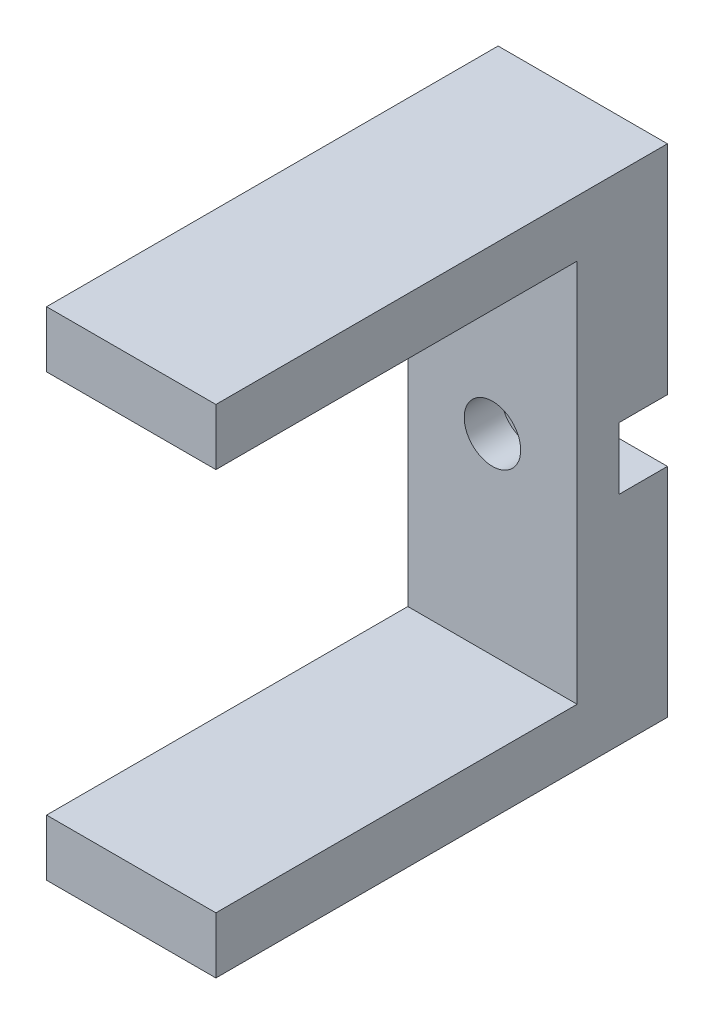
SolidWorks part; units mm, degrees
ref_plane "Front Plane" through (0, 0, 0) normal (0, 0, 1) x (1, 0, 0)
ref_plane "Top Plane" through (0, 0, 0) normal (0, 1, 0) x (1, 0, 0)
ref_plane "Right Plane" through (0, 0, 0) normal (1, 0, 0) x (0, 0, -1)
sketch "Sketch1" plane through (0, 0, 0) normal (0, 0, 1) x (1, 0, 0)
  line L1 (-12.2414, -9.222) -> (-27.2414, -9.222)
  line L2 (-12.2414, -9.222) -> (-12.2414, 34.778)
  line L3 (-12.2414, 34.778) -> (-27.2414, 34.778)
  line L4 (-27.2414, -9.222) -> (-27.2414, 34.778)
  dimension "D1" = 44
  dimension "D2" = 15
extrude "Extrude1" add sketch "Sketch1" along normal blind 40
sketch "Sketch2" plane through (0, 0, 40) normal (0, 0, 1) x (1, 0, 0)
  line L0 (-12.2414, -9.222) -> (-12.2414, 34.778) construction
  line L1 (-12.2414, 29.778) -> (-27.2414, 29.778)
  line L2 (-12.2414, 29.778) -> (-12.2414, -4.222)
  line L3 (-12.2414, -4.222) -> (-27.2414, -4.222)
  line L4 (-27.2414, 29.778) -> (-27.2414, -4.222)
  line L5 (-27.2414, 34.778) -> (-27.2414, -9.222) construction
  line L6 (-12.2414, 34.778) -> (-27.2414, 34.778) construction
  line L7 (-27.2414, -9.222) -> (-12.2414, -9.222) construction
  dimension "D1" = 5
  dimension "D2" = 5
extrude "Cut-Extrude1" cut sketch "Sketch2" against normal blind 32
sketch "Sketch3" plane through (0, 0, 0) normal (0, 0, -1) x (-1, 0, 0)
  line L0 (27.2414, 34.778) -> (27.2414, -9.222) construction
  line L1 (22.4914, 10.028) -> (27.2414, 10.028)
  line L2 (27.2414, 10.028) -> (27.2414, 15.528)
  line L3 (16.9914, 10.028) -> (12.2414, 10.028)
  line L4 (12.2414, 10.028) -> (12.2414, 15.528)
  line L5 (12.2414, -9.222) -> (12.2414, 34.778) construction
  line L6 (56.7579, 12.778) -> (-2.2752, 12.778) construction
  line L8 (27.2414, -9.222) -> (12.2414, -9.222) construction
  line L9 (12.2414, 34.778) -> (27.2414, 34.778) construction
  line L10 (19.7414, 41.163) -> (19.7414, -12.1947) construction
  line L11 (22.4914, -1.972) -> (16.9914, -1.972)
  line L12 (16.9914, -1.972) -> (16.9914, 10.028)
  line L13 (16.9914, 15.528) -> (12.2414, 15.528)
  line L14 (22.4914, 10.028) -> (22.4914, -1.972)
  line L15 (16.9914, 27.528) -> (16.9914, 15.528)
  line L16 (22.4914, 27.528) -> (16.9914, 27.528)
  line L17 (22.4914, 15.528) -> (22.4914, 27.528)
  line L18 (22.4914, 15.528) -> (27.2414, 15.528)
  point P21 (12.2414, 12.778)
  point P26 (27.2414, 12.778)
  dimension "D1" = 2.75
  dimension "D2" = 12
  dimension "D3" = 5.5
extrude "Cut-Extrude2" cut sketch "Sketch3" against normal blind 4.3
sketch "Sketch4" plane through (0, 0, 4.3) normal (0, 0, -1) x (-1, 0, 0)
  line L0 (16.9914, 10.028) -> (22.4914, 15.528) construction
  line L1 (22.4914, 10.028) -> (16.9914, 15.528) construction
  circle A0 centre (19.7414, 12.778) radius 1.25
  dimension "D1" = 2.5
extrude "Cut-Extrude3" cut sketch "Sketch4" against normal blind 4.3
sketch "Sketch5" plane through (0, 0, 8) normal (0, 0, 1) x (1, 0, 0)
  circle A0 centre (-19.7414, 12.778) radius 2.5
  circle A1 centre (-19.7414, 12.778) radius 1.25 construction
  dimension "D1" = 5
extrude "Cut-Extrude4" cut sketch "Sketch5" against normal blind 3.3
